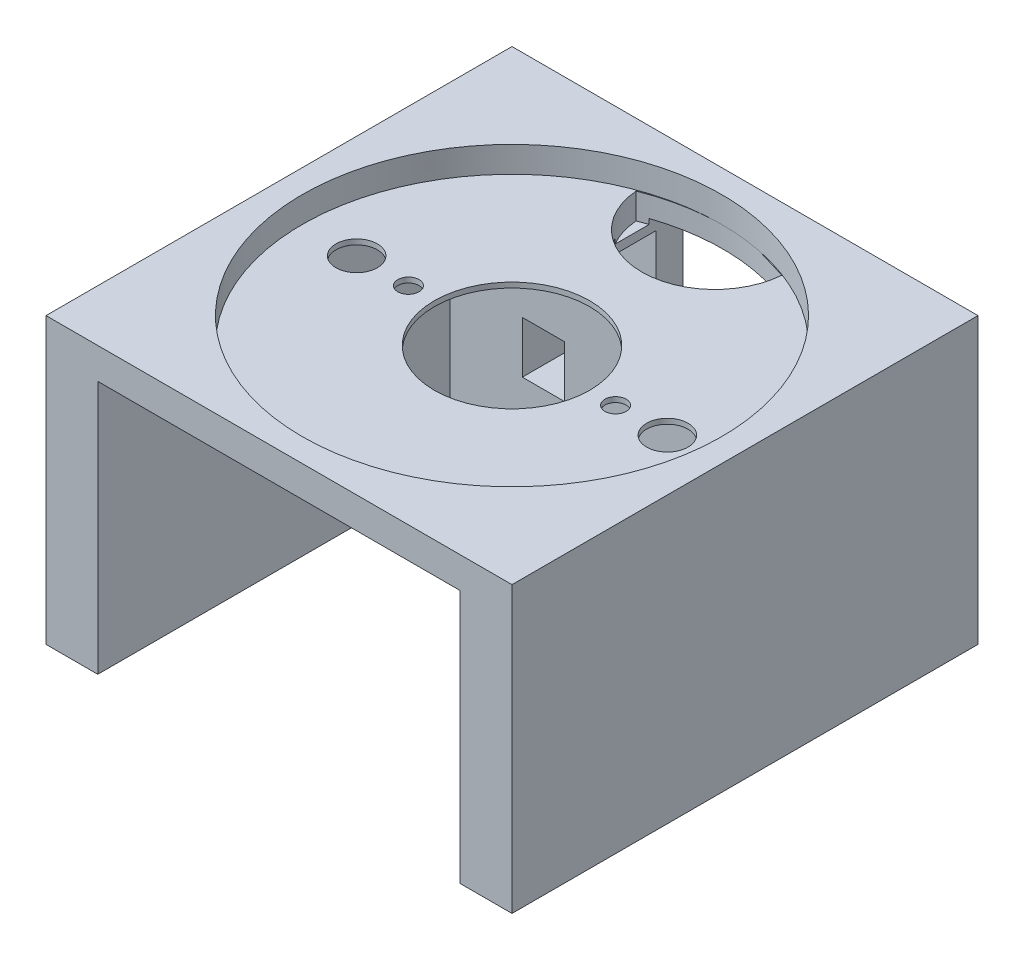
SolidWorks part; units mm, degrees
ref_plane "Front Plane" through (0, 0, 0) normal (0, 0, 1) x (1, 0, 0)
ref_plane "Top Plane" through (0, 0, 0) normal (0, 1, 0) x (1, 0, 0)
ref_plane "Right Plane" through (0, 0, 0) normal (1, 0, 0) x (0, 0, -1)
sketch "Sketch1" plane through (0, 0, 0) normal (0, 1, 0) x (1, 0, 0)
  line L2 (0, -45) -> (-45, -45)
  line L3 (-45, -45) -> (-45, 45)
  line L4 (-45, 45) -> (0, 45)
  line L5 (0, 45) -> (45, 45)
  line L6 (45, 45) -> (45, -45)
  line L7 (45, -45) -> (0, -45)
extrude "Boss-Extrude1" add sketch "Sketch1" along normal blind 10
sketch "Sketch2" plane through (0, 10, 0) normal (0, 1, 0) x (1, 0, 0)
  circle A0 centre (0, 0) radius 40.5
extrude "Cut-Extrude1" cut sketch "Sketch2" against normal blind 5 contours A0
sketch "Sketch4" plane through (0, 5, 0) normal (0, 1, 0) x (1, 0, 0)
  circle A2 centre (-20, 0) radius 2.05
  circle A3 centre (20, 0) radius 2.05
extrude "Cut-Extrude2" cut sketch "Sketch4" against normal blind 2
sketch "Sketch5" plane through (0, 5, 0) normal (0, 1, 0) x (1, 0, 0)
  circle A0 centre (0, 0) radius 15
extrude "Cut-Extrude3" cut sketch "Sketch5" against normal through all
sketch "Sketch7" plane through (0, 5, 0) normal (0, 1, 0) x (1, 0, 0)
  arc A0 (-13.8415, 37.8005) -> (14.3106, 37.8005) centre (0.2345, 38.9392) ccw
  arc A1 (-13.8415, 37.8005) -> (14.3106, 37.8005) centre (0.2345, 2.5037) cw
extrude "Cut-Extrude4" cut sketch "Sketch7" against normal blind 66 contours A0 A1
sketch "Sketch8" plane through (0, 0, 0) normal (0, -1, 0) x (1, 0, 0)
  line L0 (-45, 45) -> (45, 45)
  line L1 (45, 45) -> (45, -45)
  line L2 (45, -45) -> (-45, -45)
  line L3 (-45, -45) -> (-45, 45)
extrude "Boss-Extrude2" add sketch "Sketch8" along normal blind 45
sketch "Sketch9" plane through (0, 0, 45) normal (0, 0, 1) x (1, 0, 0)
  line L0 (-45, -45) -> (-35, -45)
  line L1 (45, -45) -> (-45, -45) construction
  line L2 (-35, -45) -> (-35, 4)
  line L3 (-35, 4) -> (35, 4)
  line L4 (35, 4) -> (35, -45)
  line L5 (35, -45) -> (-35, -45)
extrude "Cut-Extrude5" cut sketch "Sketch9" against normal blind 68 contours L2 L3 L4 L5
sketch "Sketch10" plane through (0, 0, -45) normal (0, 0, -1) x (-1, 0, 0)
  line L8 (0, 10) -> (0, -45) construction
  line L9 (-45, 10) -> (45, 10) construction
  line L13 (45, -45) -> (-45, -45) construction
  line L14 (-45, -17.5) -> (45, -17.5) construction
  line L15 (-45, 10) -> (-45, -45) construction
  line L16 (45, 10) -> (45, -45) construction
  line L29 (-12, -21) -> (-12, -25)
  line L36 (-12, -25) -> (-18, -25)
  line L37 (-12, -21) -> (-12, -2)
  line L39 (-12, -2) -> (-12, 1)
  line L40 (-12, 1) -> (12, 1)
  line L41 (12, -25) -> (12, 1)
  line L42 (12, -25) -> (18.3379, -25)
  line L43 (-18, -25) -> (-18, -37)
  line L44 (18.3379, -25) -> (18.3379, -37)
  line L45 (18.3379, -37) -> (-18, -37)
extrude "Cut-Extrude7" cut sketch "Sketch10" against normal blind 21
sketch "Sketch12" plane through (0, 0, -45) normal (0, 0, -1) x (-1, 0, 0)
  text T0 "ProtoPill\r\nDispenser\r\nTester"
extrude "Cut-Extrude9" cut sketch "Sketch12" against normal blind 4
sketch "Sketch14" plane through (0, 0, 0) normal (0, 1, 0) x (1, 0, 0)
  line L1 (0.2345, 40.5037) -> (0.2345, 24.8171) construction
  arc A0 (-13.8415, 37.8005) -> (14.3106, 37.8005) centre (0.2345, 38.9392) ccw construction
sketch "Sketch17" plane through (0, -37, 0) normal (0, 1, 0) x (1, 0, 0)
  line L0 (-0.1689, 24) -> (-0.1689, 45) construction
  line L1 (18, 24) -> (-18.3379, 24) construction
  line L2 (18, 45) -> (-18.3379, 45) construction
  line L3 (18, 34.5) -> (-18.3379, 34.5) construction
  line L4 (18, 24) -> (18, 45) construction
  line L5 (-18.3379, 24) -> (-18.3379, 45) construction
  line L6 (11.8311, 34.5) -> (11.8311, 26.5)
  line L7 (-12.1689, 34.5) -> (-12.1689, 42.5)
  line L8 (-12.1689, 34.5) -> (-12.1689, 26.5)
  line L9 (11.8311, 34.5) -> (11.8311, 42.5)
  line L10 (11.8311, 26.5) -> (-12.1689, 26.5)
  line L11 (-12.1689, 42.5) -> (11.8311, 42.5)
extrude "Cut-Extrude12" cut sketch "Sketch17" against normal blind 3
sketch "Sketch18" plane through (0, -40, 0) normal (0, 1, 0) x (1, 0, 0)
  line L0 (-0.1689, 26.5) -> (-0.1689, 42.5) construction
  line L1 (-12.1689, 26.5) -> (11.8311, 26.5) construction
  line L2 (11.8311, 42.5) -> (-12.1689, 42.5) construction
  line L3 (11.8311, 34.5) -> (-12.1689, 34.5) construction
  line L4 (11.8311, 26.5) -> (11.8311, 42.5) construction
  line L5 (-12.1689, 42.5) -> (-12.1689, 26.5) construction
  circle A0 centre (-0.1689, 34.5) radius 11.5
  dimension "D1" = 23
sketch "Sketch20" plane through (-12, 0, 0) normal (1, 0, 0) x (0, 0, -1)
  line L0 (34.5, -25) -> (34.5, 0) construction
  line L1 (24, -25) -> (45, -25) construction
  line L2 (38.4803, 0) -> (31.8859, 0) construction
  line L3 (24, -12) -> (45, -12) construction
  line L4 (24, -25) -> (24, 1) construction
  line L5 (45, -25) -> (45, 1) construction
  line L6 (29.17, -12) -> (29.17, -1.7)
  line L7 (39.83, -12) -> (39.83, -1.7)
  line L8 (39.83, -12) -> (39.83, -22.3)
  line L9 (29.17, -12) -> (29.17, -22.3)
  line L10 (29.17, -1.7) -> (39.83, -1.7)
  line L11 (39.83, -22.3) -> (29.17, -22.3)
extrude "Cut-Extrude14" cut sketch "Sketch20" against normal blind 9
sketch "Sketch21" plane through (0, 0, -29.17) normal (0, 0, -1) x (-1, 0, 0)
  line L1 (21, -1.7) -> (21, -22.3) construction
  line L2 (21, -22.3) -> (12, -22.3) construction
  line L3 (21, -22.3) -> (21, -12.3)
  line L7 (12.8896, -12.3) -> (12.8896, -22.3)
  line L8 (12.8896, -22.3) -> (21, -22.3)
  line L9 (12.8896, -12.3) -> (21, -12.3)
  dimension "D1" = 8.1104
  dimension "D2" = 10
extrude "Cut-Extrude15" cut sketch "Sketch21" against normal blind 9
sketch "Sketch22" plane through (-21, 0, 0) normal (1, 0, 0) x (0, 0, -1)
  line L0 (34.5, -1.7) -> (34.5, -22.3) construction
  line L1 (39.83, -1.7) -> (29.17, -1.7) construction
  line L2 (23, -22.3) -> (39.83, -22.3) construction
  line L3 (39.83, -12) -> (29.17, -12) construction
  line L4 (39.83, -22.3) -> (39.83, -1.7) construction
  line L5 (29.17, -1.7) -> (29.17, -12.3) construction
  circle A0 centre (34.5, -17.05) radius 1.14
  dimension "D1" = 2.28
extrude "Boss-Extrude3" add sketch "Sketch22" along normal blind 9
sketch "Sketch23" plane through (0, 0, -24) normal (0, 0, -1) x (-1, 0, 0)
  line L3 (0, 1) -> (0.1689, -37) construction
  line L4 (12, 1) -> (-12, 1) construction
  line L5 (-18, -37) -> (18.3379, -37) construction
  line L6 (-10.3077, -31.0001) -> (-10.3077, -25.0001)
  line L7 (0.1423, -31.0001) -> (-10.3077, -31.0001)
  line L11 (10.5923, -31.0001) -> (0.1423, -31.0001)
  line L12 (-10.3077, -25.0001) -> (10.5923, -25.0001)
  line L13 (10.5923, -25.0001) -> (10.5923, -31.0001)
sketch "Sketch24" plane through (12, 0, 0) normal (-1, 0, 0) x (0, 0, 1)
  line L0 (-39.83, -1.7) -> (-29.17, -1.7) construction
  line L1 (-29.17, -22.3) -> (-39.83, -22.3) construction
  line L2 (-39.83, -22.3) -> (-39.83, -1.7) construction
  line L3 (-29.17, -1.7) -> (-29.17, -22.3) construction
  line L4 (-39.83, -1.7) -> (-29.17, -1.7)
  line L5 (-29.17, -22.3) -> (-39.83, -22.3)
  line L6 (-39.83, -22.3) -> (-39.83, -1.7)
  line L7 (-29.17, -1.7) -> (-29.17, -22.3)
  circle A0 centre (-34.5, -17.05) radius 1.14 construction
  circle A1 centre (-34.5, -17.05) radius 1.14
extrude "Cut-Extrude16" cut sketch "Sketch24" against normal blind 9
sketch "Sketch25" plane through (0, 0, -29.17) normal (0, 0, -1) x (-1, 0, 0)
  line L0 (-21, -22.3) -> (-21, -12.3)
  line L1 (-21, -22.3) -> (-21, -1.7) construction
  line L2 (-21, -12.3) -> (-12.89, -12.3)
  line L3 (-12.89, -12.3) -> (-12.89, -22.3)
  line L4 (-21, -22.3) -> (-12, -22.3) construction
  line L5 (-12.89, -22.3) -> (-21, -22.3)
extrude "Cut-Extrude17" cut sketch "Sketch25" against normal blind 9
extrude "Cut-Extrude20" cut sketch "Sketch23" against normal blind 24.7
sketch "Sketch31" plane through (0, 5, 0) normal (0, 1, 0) x (1, 0, 0)
  circle A0 centre (-30, 0) radius 4
  circle A1 centre (30, 0) radius 4
extrude "Cut-Extrude21" cut sketch "Sketch31" against normal blind 10
